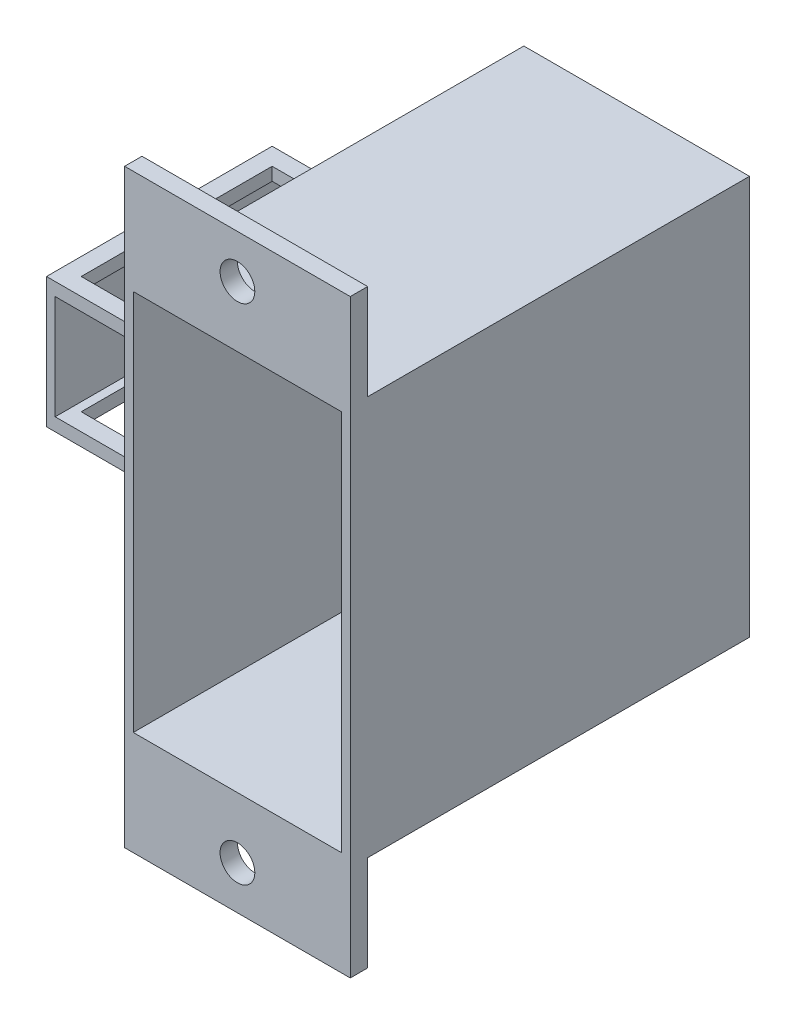
SolidWorks part; units mm, degrees
ref_plane "Front Plane" through (0, 0, 0) normal (0, 0, 1) x (1, 0, 0)
ref_plane "Top Plane" through (0, 0, 0) normal (0, 1, 0) x (1, 0, 0)
ref_plane "Right Plane" through (0, 0, 0) normal (1, 0, 0) x (0, 0, -1)
sketch "Sketch1" plane through (0, 0, 0) normal (0, 0, 1) x (1, 0, 0)
  line L1 (-6.5, 11.5) -> (6.5, 11.5)
  line L2 (-6.5, 11.5) -> (-6.5, -11.5)
  line L3 (-6.5, -11.5) -> (6.5, -11.5)
  line L4 (6.5, 11.5) -> (6.5, -11.5)
  line L5 (-6.5, 11.5) -> (6.5, -11.5) construction
  line L6 (-6.5, -11.5) -> (6.5, 11.5) construction
  line L7 (-6, 11) -> (6, 11)
  line L8 (-6, 11) -> (-6, -11)
  line L9 (-6, -11) -> (6, -11)
  line L10 (6, 11) -> (6, -11)
  line L11 (-6, 11) -> (6, -11) construction
  line L12 (-6, -11) -> (6, 11) construction
  point P0 (0, 0)
  point P6 (0, 0)
  dimension "D1" = 22
  dimension "D2" = 12
  dimension "D3" = 13
  dimension "D4" = 23
extrude "Boss-Extrude1" add sketch "Sketch1" along normal blind 23 contours L2 L3 L4 L1
extrude "Cut-Extrude1" cut sketch "Sketch1<3>" along normal up to next contours L7 L10 L9 L8
sketch "Sketch1<3>" plane through (0, 0, 0) normal (0, 0, 1) x (1, 0, 0) same geometry as "Sketch1"
ref_plane "Plane1" through (0, 0, 23) normal (0, 0, 1) x (1, 0, 0)
sketch "Sketch2" plane through (0, 0, 23) normal (0, 0, 1) x (1, 0, 0)
  line L0 (-6.5, 11.5) -> (-6.5, 17)
  line L1 (-6.5, 17) -> (6.5, 17)
  line L2 (6.5, 17) -> (6.5, 11.5)
  line L3 (6.5, 11.5) -> (-6.5, 11.5)
  line L4 (7.15, 0) -> (-7.15, 0) construction
  line L5 (6.5, -17) -> (6.5, -11.5)
  line L6 (-6.5, -17) -> (6.5, -17)
  line L7 (-6.5, -11.5) -> (-6.5, -17)
  line L8 (6.5, -11.5) -> (-6.5, -11.5)
  circle A0 centre (0, 14.5) radius 1
  circle A1 centre (0, -14.5) radius 1
  point P14 (0, 0)
  point P16 (0, 0)
  dimension "D3" = 2
  dimension "D1" = 5.5
  dimension "D2" = 3
extrude "Boss-Extrude2" add sketch "Sketch2" against normal blind 1
ref_plane "Plane3" through (-6.5, 0, 0) normal (-1, 0, 0) x (0, 0, 1)
sketch "Sketch4" plane through (-6.5, 0, 0) normal (-1, 0, 0) x (0, 0, 1)
  line L0 (0, 0) -> (23, 0) construction
  line L1 (23, -7.15) -> (23, 7.15) construction
  line L2 (11, 11.5) -> (11, -11.5) construction
  line L3 (22, 11.5) -> (0, 11.5) construction
  line L4 (22, -11.5) -> (0, -11.5) construction
  line L10 (4.5, 3.75) -> (17.5, 3.75)
  line L11 (4.5, 3.75) -> (4.5, -3.75)
  line L12 (4.5, -3.75) -> (17.5, -3.75)
  line L13 (17.5, 3.75) -> (17.5, -3.75)
  line L14 (4.5, 3.75) -> (17.5, -3.75) construction
  line L15 (4.5, -3.75) -> (17.5, 3.75) construction
  point P11 (11.5, 0)
  point P12 (11, 0)
  point P13 (11, 0)
  dimension "D1" = 7.5
  dimension "D2" = 13
extrude "Boss-Extrude3" add sketch "Sketch4" along normal blind 10
ref_plane "Plane4" through (0, -3.75, 0) normal (0, -1, 0) x (-1, 0, 0)
sketch "Sketch5" plane through (0, -3.75, 0) normal (0, -1, 0) x (-1, 0, 0)
  line L0 (16.5, -11) -> (6.5, -11) construction
  line L1 (16.5, -4.5) -> (16.5, -17.5) construction
  line L2 (6.5, -12.65) -> (6.5, 12.65) construction
  line L3 (11.5, -17.5) -> (11.5, -4.5) construction
  line L4 (16.5, -17.5) -> (6.5, -17.5) construction
  line L5 (16.5, -4.5) -> (6.5, -4.5) construction
  line L7 (15.5, -16.5) -> (7.5, -16.5)
  line L8 (15.5, -16.5) -> (15.5, -5.5)
  line L9 (15.5, -5.5) -> (7.5, -5.5)
  line L10 (7.5, -16.5) -> (7.5, -5.5)
  line L11 (15.5, -16.5) -> (7.5, -5.5) construction
  line L12 (15.5, -5.5) -> (7.5, -16.5) construction
  point P12 (11.5, -11)
  dimension "D1" = 11
  dimension "D2" = 8
extrude "Cut-Extrude2" cut sketch "Sketch5" against normal up to next
ref_plane "Plane5" through (0, 0, 17.5) normal (0, 0, 1) x (1, 0, 0)
sketch "Sketch6" plane through (0, 0, 17.5) normal (0, 0, 1) x (1, 0, 0)
  line L0 (-16.5, 0) -> (-6.5, 0) construction
  line L1 (-16.5, -3.75) -> (-16.5, 3.75) construction
  line L2 (-6.5, 11.5) -> (-6.5, -11.5) construction
  line L3 (-11.5, 3.75) -> (-11.5, -3.75) construction
  line L4 (-16.5, 3.75) -> (-6.5, 3.75) construction
  line L5 (-5.5, -3.75) -> (5.5, -3.75) construction
  line L7 (-16, 3) -> (-7, 3)
  line L8 (-16, 3) -> (-16, -3)
  line L9 (-16, -3) -> (-7, -3)
  line L10 (-7, 3) -> (-7, -3)
  line L11 (-16, 3) -> (-7, -3) construction
  line L12 (-16, -3) -> (-7, 3) construction
  point P12 (-11.5, 0)
  dimension "D1" = 9
  dimension "D2" = 6
extrude "Cut-Extrude3" cut sketch "Sketch6" against normal up to next
ref_plane "Plane6" through (-16.5, 0, 0) normal (-1, 0, 0) x (0, 0, 1)
sketch "Sketch7" plane through (-16.5, 0, 0) normal (-1, 0, 0) x (0, 0, 1)
  line L0 (4.5, 0) -> (17.5, 0) construction
  line L1 (4.5, 3.75) -> (4.5, -3.75) construction
  line L2 (17.5, -3.75) -> (17.5, 3.75) construction
  line L3 (11, 3.75) -> (11, -3.75) construction
  line L4 (17.5, 3.75) -> (4.5, 3.75) construction
  line L5 (4.5, -3.75) -> (17.5, -3.75) construction
  circle A0 centre (11, 0) radius 1.5 construction
  dimension "D1" = 3
